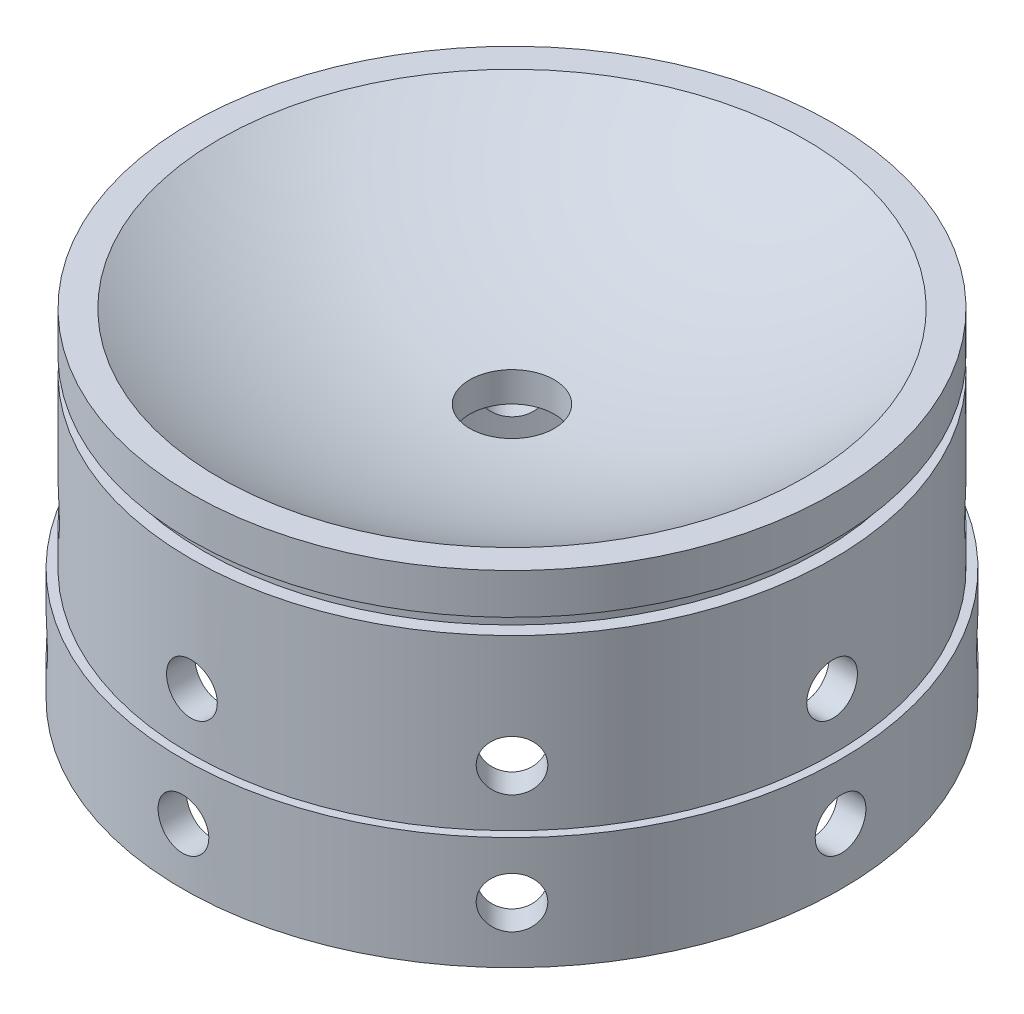
SolidWorks part; units mm, degrees
ref_plane "Front Plane" through (0, 0, 0) normal (0, 0, 1) x (1, 0, 0)
ref_plane "Top Plane" through (0, 0, 0) normal (0, 1, 0) x (1, 0, 0)
ref_plane "Right Plane" through (0, 0, 0) normal (1, 0, 0) x (0, 0, -1)
sketch "Sketch1" plane through (0, 0, 0) normal (0, 0, 1) x (1, 0, 0)
  line L0 (0, 0) -> (0, 6.35)
  line L1 (0, 0) -> (72.39, 0)
  line L2 (72.39, 0) -> (72.39, 12.7)
  line L3 (72.39, 12.7) -> (69.469, 12.7)
  line L4 (69.469, 12.7) -> (69.469, 16.256)
  line L5 (69.469, 16.256) -> (72.39, 16.256)
  line L6 (72.39, 16.256) -> (72.39, 25.4)
  line L9 (72.39, 6.35) -> (0, 6.35) construction
  line L10 (72.39, 0) -> (72.39, -25.4)
  line L11 (72.39, -25.4) -> (66.04, -25.4)
  line L12 (66.04, -25.4) -> (66.04, 0)
  line L13 (74.93, 68.1653) -> (74.93, 53.6699) construction
  line L14 (67.945, -50.8) -> (67.945, -25.4)
  line L15 (67.945, -50.8) -> (74.295, -50.8)
  line L16 (9.525, 6.7164) -> (9.525, 0)
  line L17 (73.025, 45.3691) -> (73.025, 21.7883) construction
  line L18 (74.295, -50.8) -> (74.295, -25.4)
  line L19 (74.295, -25.4) -> (72.39, -25.4)
  line L20 (72.39, 25.4) -> (66.04, 25.4)
  arc A1 (0, 6.35) -> (66.04, 25.4) centre (0, 130.3443) ccw
  point P10 (0, 0)
  point P24 (66.8803, 25.4)
  dimension "D1" = 72.39
  dimension "D9" = 6.35
  dimension "D12" = 9.525
  dimension "D3" = 12.7
  dimension "D4" = 3.556
  dimension "D2" = 73.025
  dimension "D13" = 3.556
  dimension "D6" = 6.35
  dimension "D7" = 25.4
  dimension "D8" = 74.93
  dimension "D10" = 25.4
  dimension "D11" = 74.295
  dimension "D5" = 25.4
  dimension "D14" = 6.35
revolve "Revolve1" add sketch "Sketch1" angle 360 about L0 region at (48.3195, 8.6296, 0) region at (69.215, -12.7, 0) region at (71.12, -38.1, 0)
hole_wizard "1/2 (0.45) Diameter Hole3" positions "3DSketch5" profile "Sketch8" hole size "1/2" standard "ANSI Inch"
sketch3d "3DSketch5"
  line L0 (0, -25.4, 0) -> (0, 0, 0) construction
  line L2 (0, -12.7, 0) -> (72.39, -12.7, 0)
  circle A8 centre (0, -25.4, 0) radius 72.39 construction
  circle A9 centre (0, -25.4, 0) radius 72.39
  point P0 (72.39, -12.7, 0)
  point P41 (0, -97.79, 0)
  point P43 (0, -97.79, 0)
  point P53 (72.39, -12.7, 0)
sketch "Sketch8" plane through (72.39, -12.7, 0) normal (0, 1, 0) x (0, 0, -1)
  line L0 (0, 0) -> (0, 75.8229)
  line L1 (0, 75.8229) -> (5.715, 72.389)
  line L2 (5.715, 72.389) -> (5.715, 0)
  line L5 (5.715, 0) -> (0, 0)
  line L10 (0, 75.8229) -> (-5.715, 72.389) construction
  line L11 (0, -6.35) -> (0, 107.95) construction
  dimension "Hole Dia." = 11.43
  dimension "Hole Depth" = 72.389
  dimension "Drill Angle" = 118
hole_wizard "1/2 (0.45) Diameter Hole2" positions "3DSketch6" profile "Sketch9" hole size "1/2" standard "ANSI Inch"
sketch3d "3DSketch6"
  line L0 (0, -25.4, 0) -> (0, -50.8, 0)
  line L2 (0, -38.1, 0) -> (74.295, -38.1, 0)
  circle A0 centre (0, -50.8, 0) radius 74.295 construction
  circle A1 centre (0, -25.4, 0) radius 74.295 construction
  circle A2 centre (0, -50.8, 0) radius 74.295
  circle A3 centre (0, -25.4, 0) radius 74.295
  point P0 (74.295, -38.1, 0)
  point P5 (0, -125.095, 0)
  point P8 (0, -99.695, 0)
  point P10 (0, -125.095, 0)
  point P12 (0, -99.695, 0)
sketch "Sketch9" plane through (74.295, -38.1, 0) normal (0, 1, 0) x (0, 0, -1)
  line L0 (0, 0) -> (0, 77.7279)
  line L1 (0, 77.7279) -> (5.715, 74.294)
  line L2 (5.715, 74.294) -> (5.715, 0)
  line L5 (5.715, 0) -> (0, 0)
  line L10 (0, 77.7279) -> (-5.715, 74.294) construction
  line L11 (0, -6.35) -> (0, 107.95) construction
  dimension "Hole Dia." = 11.43
  dimension "Hole Depth" = 74.294
  dimension "Drill Angle" = 118
ref_axis "CenterAxis" through (0, 6.7164, 0) along (0, -1, 0)
chamfer "Chamfer1" distance 2.54 angle 45 1 edges at (0, -25.4, -67.945)
pattern_circular "CirPattern1" count 8 over 360 about axis through (0, -25.4, 0) along (0, -1, 0) of "1/2 (0.45) Diameter Hole3", "1/2 (0.45) Diameter Hole2"
equation "\"D1@Sketch1\"=(5.75/2)-(0.025in)"
equation "\"D12@Sketch1\"=0.75/2"
equation "\"D2@Sketch1\"=5.75/2"
equation "\"D8@Sketch1\"=5.9/2"
equation "\"D11@Sketch1\"=5.9/2 - (0.025in)"
